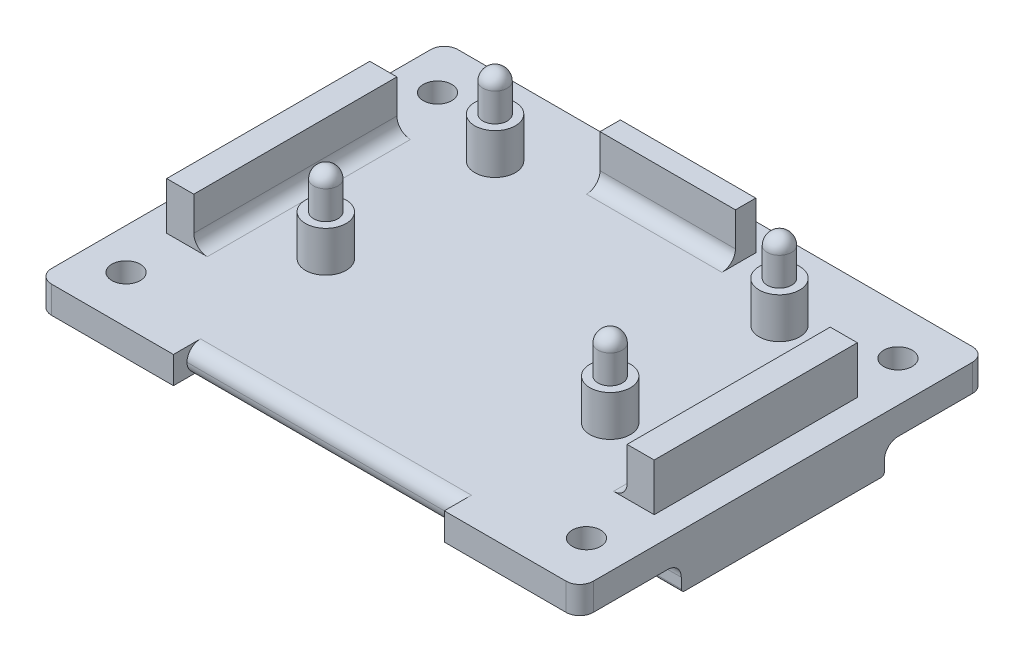
SolidWorks part; units mm, degrees
material "ABS"
ref_plane "Front Plane" through (0, 0, 0) normal (0, 0, 1) x (1, 0, 0)
ref_plane "Top Plane" through (0, 0, 0) normal (0, 1, 0) x (1, 0, 0)
ref_plane "Right Plane" through (0, 0, 0) normal (1, 0, 0) x (0, 0, -1)
sketch "Sketch3" plane through (0, 0, 0) normal (0, 1, 0) x (1, 0, 0)
  line L1 (-20, 15) -> (20, 15)
  line L2 (-20, 15) -> (-20, -15)
  line L3 (-20, -15) -> (20, -15)
  line L4 (20, 15) -> (20, -15)
  line L5 (-20, 15) -> (20, -15) construction
  line L6 (-20, -15) -> (20, 15) construction
  point P0 (0, 0)
  dimension "D1" = 40
  dimension "D2" = 30
extrude "Boss-Extrude1" add sketch "Sketch3" along normal blind 2
sketch "Sketch4" plane through (0, 2, 0) normal (0, 1, 0) x (1, 0, 0)
  line L1 (-9, 9.25) -> (9, 9.25)
  line L2 (-10.5, 7.75) -> (-10.5, -1.75)
  line L3 (-9, -3.25) -> (9, -3.25)
  line L4 (10.5, 7.75) -> (10.5, -1.75)
  line L5 (-9.2111, 8.4828) -> (9.2111, -2.4828) construction
  line L6 (-9.2111, -2.4828) -> (9.2111, 8.4828) construction
  circle A0 centre (-10.5, 9.25) radius 1.5
  circle A1 centre (10.5, 9.25) radius 1.5
  circle A2 centre (10.5, -3.25) radius 1.5
  circle A3 centre (-10.5, -3.25) radius 1.5
  point P0 (0, 0)
  dimension "D3" = 3
  dimension "D4" = 3
  dimension "D5" = 3
  dimension "D6" = 3
  dimension "D1" = 21
  dimension "D2" = 12.5
extrude "Boss-Extrude2" add sketch "Sketch4" along normal blind 3 contours A0 | A1 | A2 | A3 region at (-10.5, 2, -9.25) region at (10.5, 2, -9.25) region at (-10.5, 2, 3.25) region at (10.5, 2, 3.25)
fillet "Fillet1" radius 1 2 edges at (20, 1, -15) (-20, 1, -15)
sketch "Sketch8" plane through (0, 2, 0) normal (0, 1, 0) x (1, 0, 0)
  line L0 (-20, -15) -> (20, -15) construction
  line L1 (-10, -15) -> (10, -15)
  line L2 (-10, -15) -> (-10, -14)
  line L3 (-10, -14) -> (10, -14)
  line L4 (10, -15) -> (10, -14)
  line L5 (-20, 14) -> (-20, -15) construction
  dimension "D1" = 1
  dimension "D2" = 20
  dimension "D3" = 10
extrude "Cut-Extrude2" cut sketch "Sketch8" against normal blind 2
fillet "Fillet3" radius 1 2 edges at (0, 0, 14) (0, 2, 14)
ref_plane "Plane1" through (0, 5, 0) normal (0, 1, 0) x (1, 0, 0)
sketch "Sketch9" plane through (0, 5, 0) normal (0, 1, 0) x (1, 0, 0)
  circle A0 centre (-10.5, 9.25) radius 0.9
  dimension "D1" = 1.8
extrude "Boss-Extrude5" add sketch "Sketch9" along normal blind 3
pattern_linear "LPattern3" count 2 spacing 21 along (1, 0, 0) count 2 spacing 12.5 along (0, 0, 1) of "Boss-Extrude5"
fillet "Fillet4" radius 0.9 4 edges at (10.5, 8, 4.15) (10.5, 8, -8.35) (-10.5, 8, 4.15) (-10.5, 8, -8.35)
fillet "Fillet5" radius 1 2 edges at (20, 1, 15) (-20, 1, 15)
sketch "Sketch11" plane through (0, 2, 0) normal (0, 1, 0) x (1, 0, 0)
  line L0 (-19, -15) -> (-10, -15) construction
  line L1 (-20, 14) -> (-20, -14) construction
  circle A0 centre (-17, -11.5) radius 1.05
  dimension "D1" = 2.1
  dimension "D4" = 3.5
  dimension "D2" = 3.5
  dimension "D3" = 3
extrude "Cut-Extrude3" cut sketch "Sketch11" against normal through all
pattern_linear "LPattern4" count 2 spacing 23 along (0, 0, -1) count 2 spacing 34 along (1, 0, 0) of "Cut-Extrude3"
sketch "Sketch12" plane through (0, 0, 0) normal (0, -1, 0) x (-1, 0, 0)
  line L0 (20, 1) -> (-20, 1)
  line L1 (-19, 15) -> (19, 15) construction
  line L2 (20, 14) -> (20, -14) construction
  line L3 (20, 1) -> (20, 3.5)
  line L4 (-20, 1) -> (-20, 3.5)
  line L5 (20, 3.5) -> (-20, 3.5)
  dimension "D1" = 2.5
  dimension "D2" = 11.5
  dimension "D3" = 40
extrude "Boss-Extrude7" add sketch "Sketch12" along normal blind 10
sketch "Sketch13" plane through (0, 0, -3.5) normal (0, 0, -1) x (-1, 0, 0)
  line L0 (0, -5) -> (12, -5)
  line L1 (20, 0) -> (-20, 0) construction
  line L2 (20, -10) -> (20, 0) construction
  circle A0 centre (12, -5) radius 2
  circle A1 centre (0, -5) radius 2
  dimension "D2" = 4
  dimension "D3" = 4
  dimension "D1" = 5
  dimension "D4" = 20
  dimension "D5" = 12
extrude "Cut-Extrude4" cut sketch "Sketch13" against normal blind 10 contours A1 | A0 region at (-12, -3.0566, -3.5) region at (1.9434, -5, -3.5)
sketch "Sketch14" plane through (0, 2, 0) normal (0, 1, 0) x (1, 0, 0)
  line L0 (-20, 14) -> (-20, -14) construction
  line L1 (-18, 7.5) -> (-16, 7.5)
  line L2 (-18, 7.5) -> (-18, -7.5)
  line L3 (-18, -7.5) -> (-16, -7.5)
  line L4 (-16, 7.5) -> (-16, -7.5)
  line L5 (16, 7.5) -> (18, 7.5)
  line L6 (16, 7.5) -> (16, -7.5)
  line L7 (16, -7.5) -> (18, -7.5)
  line L8 (18, 7.5) -> (18, -7.5)
  line L9 (-5, 13) -> (5, 13)
  line L10 (-5, 13) -> (-5, 11.5)
  line L11 (-5, 11.5) -> (5, 11.5)
  line L12 (5, 13) -> (5, 11.5)
  line L13 (19, 15) -> (-19, 15) construction
  line L14 (20, -14) -> (20, 14) construction
  line L15 (-19, -15) -> (-10, -15) construction
  line L16 (10, -15) -> (19, -15) construction
  dimension "D1" = 2
  dimension "D2" = 2
  dimension "D3" = 2
  dimension "D4" = 1.5
  dimension "D5" = 2
  dimension "D6" = 2
  dimension "D7" = 15
  dimension "D8" = 15
  dimension "D9" = 10
  dimension "D10" = 15
  dimension "D11" = 7.5
  dimension "D12" = 7.5
extrude "Boss-Extrude8" add sketch "Sketch14" along normal blind 3.5
fillet "Fillet6" radius 1 3 edges at (0, 2, -11.5) (16, 2, 0) (-16, 2, 0)
sketch "Sketch15" plane through (-20, 0, 0) normal (-1, 0, 0) x (0, 0, 1)
  line L1 (-15.5352, 0) -> (17.8985, 0)
  line L2 (-15.5352, 0) -> (-15.5352, -17.8791)
  line L3 (-15.5352, -17.8791) -> (17.8985, -17.8791)
  line L4 (17.8985, 0) -> (17.8985, -17.8791)
  dimension "D1" = 0
extrude "Cut-Extrude5" cut sketch "Sketch15" against normal through all both and the other way through all
sketch "Sketch16" plane through (0, 0, 0) normal (0, -1, 0) x (1, 0, 0)
  line L0 (20, 14) -> (20, -14) construction
  line L1 (-20, -7.5) -> (20, -7.5)
  line L2 (-20, -7.5) -> (-20, 7.5)
  line L3 (-20, 7.5) -> (20, 7.5)
  line L4 (20, -7.5) -> (20, 7.5)
  line L5 (-20, -7.5) -> (20, 7.5) construction
  line L6 (-20, 7.5) -> (20, -7.5) construction
  circle A0 centre (-17, 11.5) radius 1.05 construction
  point P0 (0, 0)
  dimension "D1" = 4
extrude "Boss-Extrude9" add sketch "Sketch16" along normal blind 2
fillet "Fillet8" radius 1 1 edges at (0, 0, -7.5)
fillet "Fillet9" radius 1 1 edges at (0, 0, 7.5)
fillet "Fillet10" radius 0.25 2 edges at (0, -2, -7.5) (0, -2, 7.5)
